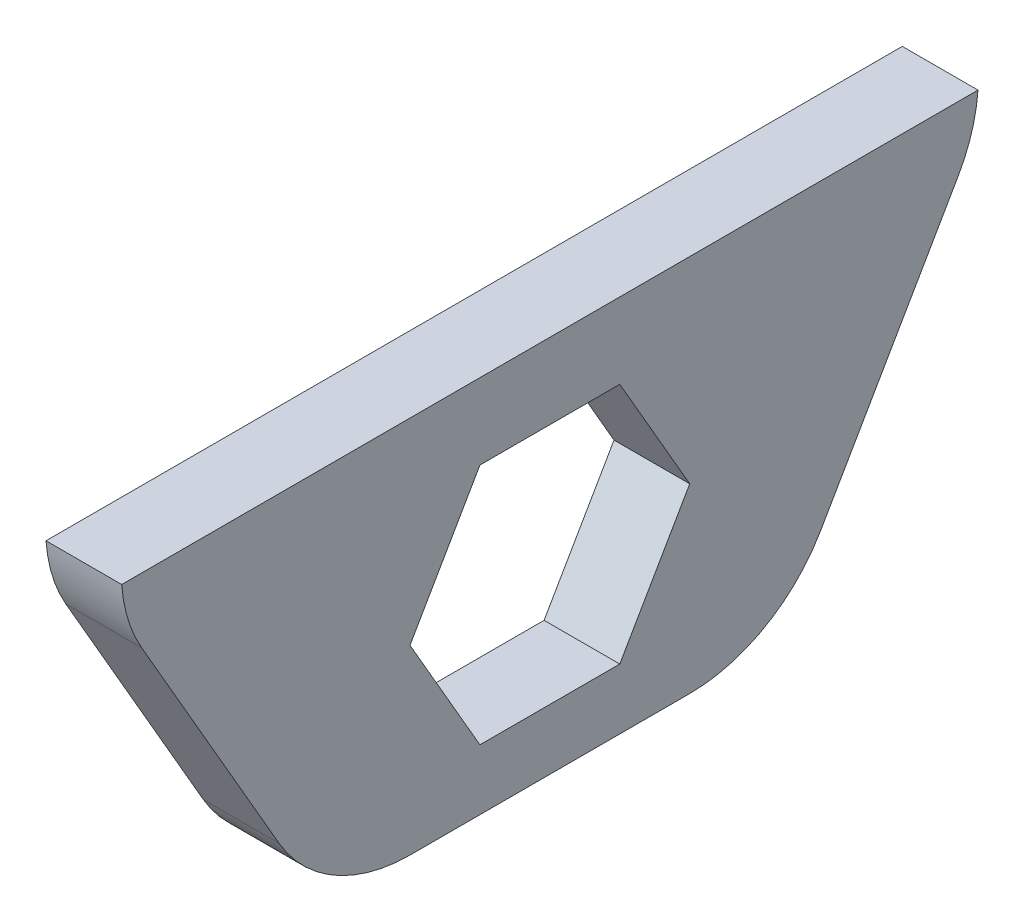
SolidWorks part; units mm, degrees
ref_plane "정면" through (0, 0, 0) normal (0, 0, 1) x (1, 0, 0)
ref_plane "윗면" through (0, 0, 0) normal (0, 1, 0) x (1, 0, 0)
ref_plane "우측면" through (0, 0, 0) normal (1, 0, 0) x (0, 0, -1)
sketch "스케치1" plane through (0, 0, 0) normal (1, 0, 0) x (0, 0, -1)
  line L0 (0, 0) -> (-13.2791, 23)
  line L1 (43.2791, 23) -> (43.2791, 25)
  line L2 (43.2791, 23) -> (30, 0)
  line L3 (30, 0) -> (0, 0)
  line L5 (43.2791, 25) -> (-13.2791, 25)
  line L6 (-13.2791, 25) -> (-13.2791, 23)
  dimension "D1" = 2
  dimension "D2" = 120
  dimension "D3" = 120
  dimension "D4" = 30
  dimension "D5" = 25
extrude "보스-돌출1" add sketch "스케치1" along normal blind 5
fillet "필렛1" radius 10 4 edges at (2.5, 23, -43.2791) (2.5, 0, -30) (2.5, 0, 0) (2.5, 23, 13.2791)
sketch "스케치2" plane through (5, 0, 0) normal (1, 0, 0) x (0, 0, -1)
  line L0 (15, 25) -> (15, 12) construction
  line L1 (43.2791, 25) -> (-13.2791, 25) construction
  line L3 (19.6188, 20) -> (10.3812, 20)
  line L4 (10.3812, 20) -> (5.7624, 12)
  line L5 (5.7624, 12) -> (10.3812, 4)
  line L6 (10.3812, 4) -> (19.6188, 4)
  line L7 (19.6188, 4) -> (24.2376, 12)
  line L8 (24.2376, 12) -> (19.6188, 20)
  circle A0 centre (15, 12) radius 8 construction
  dimension "D1" = 13
  dimension "D2" = 16
extrude "컷-돌출1" cut sketch "스케치2" against normal blind 10
sketch "스케치3" plane through (5, 0, 0) normal (1, 0, 0) x (0, 0, -1)
  line L0 (10.3812, 20) -> (19.6188, 4) construction
  point P4 (15, 12)
